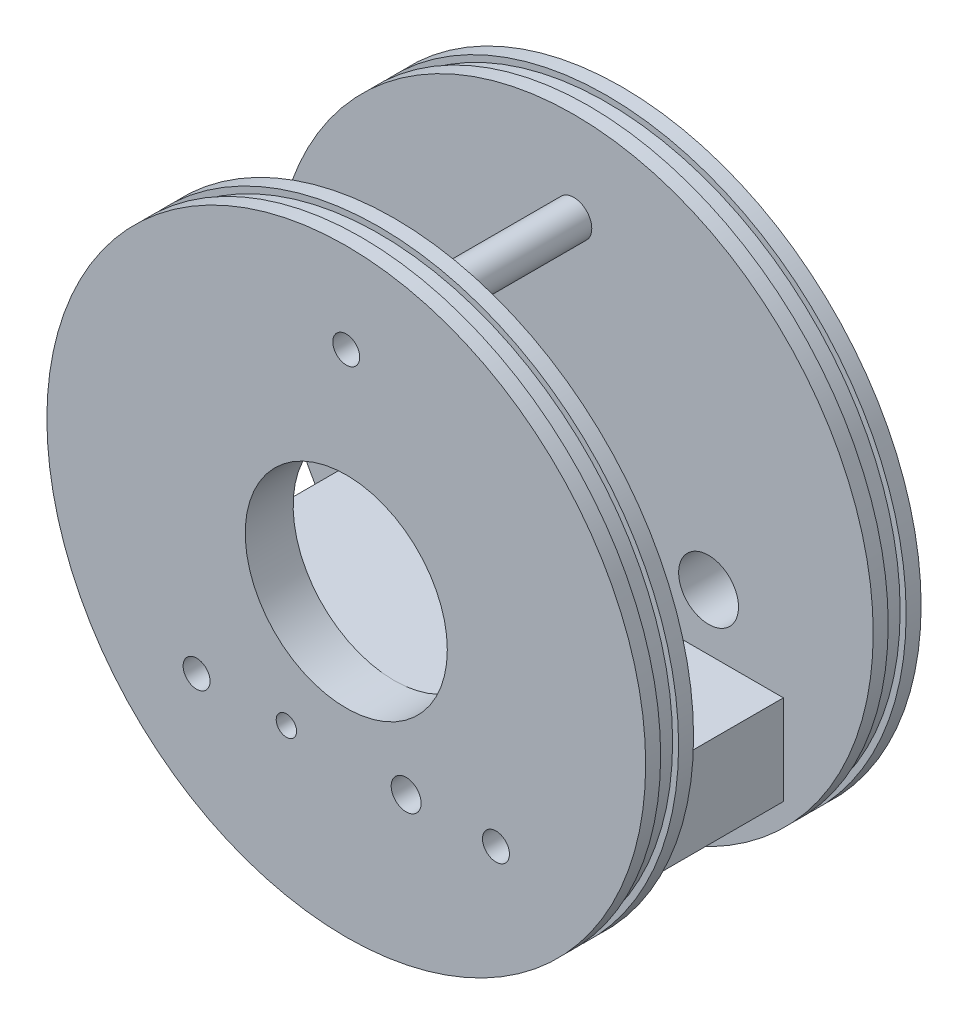
SolidWorks part; units mm, degrees
ref_plane "Front Plane" through (0, 0, 0) normal (0, 0, 1) x (1, 0, 0)
ref_plane "Top Plane" through (0, 0, 0) normal (0, 1, 0) x (1, 0, 0)
ref_plane "Right Plane" through (0, 0, 0) normal (1, 0, 0) x (0, 0, -1)
sketch "Sketch2" plane through (0, 0, 0) normal (0, 0, 1) x (1, 0, 0)
  circle A0 centre (0, 0) radius 98
  circle A1 centre (0, 0) radius 100
  dimension "D1" = 196
  dimension "D2" = 200
extrude "Boss-Extrude1" add sketch "Sketch2" along normal blind 8 and the other way blind 8 contours A1 A0 | A0 region at (-99.7172, 0, 0)
extrude "Cut-Extrude1" cut sketch "Sketch2<5>" against normal blind 3 and the other way blind 3
sketch "Sketch2<5>" plane through (0, 0, 0) normal (0, 0, 1) x (1, 0, 0) same geometry as "Sketch2"
sketch "Sketch3" plane through (0, 0, 8) normal (0, 0, 1) x (1, 0, 0)
  line L0 (0, 33.75) -> (0, -33.75) construction
  line L1 (41.5, 33.75) -> (-78.5, 33.75)
  line L2 (41.5, 33.75) -> (41.5, -33.75)
  line L3 (41.5, -33.75) -> (-78.5, -33.75) construction
  line L4 (-78.5, 33.75) -> (-78.5, -33.75) construction
  line L5 (31, 33.75) -> (31, -33.75) construction
  line L6 (41.5, 0) -> (-78.5, 0) construction
  line L7 (-78.5, 28.75) -> (-43.5, 28.75)
  line L8 (-43.5, 28.75) -> (-43.5, -33.75)
  line L9 (-78.5, 33.75) -> (-78.5, 28.75)
  line L10 (-43.5, -33.75) -> (41.5, -33.75)
  circle A0 centre (0, 0) radius 31
  circle A1 centre (0, 0) radius 33.75
  point P9 (0, 0)
  dimension "D3" = 62
  dimension "D7" = 67.5
  dimension "D1" = 10.5
  dimension "D2" = 120
  dimension "D4" = 67.5
  dimension "D5" = 5
  dimension "D6" = 35
sketch "Sketch4" plane through (0, 0, -8) normal (0, 0, 1) x (1, 0, 0)
  line L0 (0, 33.75) -> (0, -33.75) construction
  line L1 (41.5, 33.75) -> (-78.5, 33.75)
  line L2 (41.5, 33.75) -> (41.5, -33.75)
  line L3 (41.5, -33.75) -> (-78.5, -33.75) construction
  line L4 (-78.5, 33.75) -> (-78.5, -33.75) construction
  line L5 (31, 33.75) -> (31, -33.75) construction
  line L6 (41.5, 0) -> (-78.5, 0) construction
  line L7 (-78.5, 28.75) -> (-43.5, 28.75)
  line L8 (-43.5, 28.75) -> (-43.5, -33.75)
  line L9 (-78.5, 33.75) -> (-78.5, 28.75)
  line L10 (-43.5, -33.75) -> (41.5, -33.75)
  circle A0 centre (0, 0) radius 31
  point P9 (0, 0)
  point P16 (204.2739, 34.924)
  point P18 (372.8764, 103.8868)
  point P19 (0, 0)
  point P21 (0, 0)
  dimension "D3" = 62
  dimension "D1" = 10.5
  dimension "D2" = 120
  dimension "D4" = 67.5
  dimension "D5" = 5
  dimension "D6" = 35
ref_plane "Plane1" through (0, -33.75, 0) normal (0, 1, 0) x (1, 0, 0)
pattern_linear "LPattern1" count 2 spacing 76 along (0, 0, -1) of bodies 102 105
sketch "Sketch5" plane through (0, -33.75, 0) normal (0, 1, 0) x (1, 0, 0)
  line L0 (0, 8) -> (0, 43) construction
  line L1 (70, 8) -> (-70, 8)
  line L2 (70, 8) -> (70, 68)
  line L3 (70, 68) -> (-70, 68)
  line L4 (-70, 8) -> (-70, 68)
  circle A0 centre (0, 43) radius 3.2
  dimension "D4" = 6.4
  dimension "D1" = 60
  dimension "D2" = 140
  dimension "D3" = 35
extrude "Boss-Extrude2" add sketch "Sketch5" against normal blind 30 contours A0 | L3 L4 L1 L2 region at (0, -33.75, -43)
sketch "Sketch7" plane through (0, 0, 8) normal (0, 0, 1) x (1, 0, 0)
  line L0 (0, -33.75) -> (0, -48.75) construction
  line L1 (-50, -48.75) -> (50, -48.75) construction
  line L2 (0, -48.75) -> (20, -48.75) construction
  line L3 (0, -48.75) -> (-20, -48.75) construction
  circle A0 centre (-50, -48.75) radius 4.5
  circle A1 centre (50, -48.75) radius 4.5
  circle A3 centre (-20, -48.75) radius 3.4
  circle A4 centre (20, -48.75) radius 5
  point P7 (0, -48.75)
  dimension "D3" = 9
  dimension "D4" = 9
  dimension "D5" = 20
  dimension "D7" = 6.8
  dimension "D8" = 10
  dimension "D1" = 100
  dimension "D2" = 15
  dimension "D6" = 20
extrude "Cut-Extrude2" cut sketch "Sketch7" against normal blind 167
extrude "Cut-Extrude3" cut sketch "Sketch3" against normal blind 43 contours L1 A1 L10 A0 | A0 | A1 region at (23.1899, 23.1899, 8) region at (0, 0, 8)
sketch "Sketch10" plane through (0, 0, -8) normal (0, 0, -1) x (-1, 0, 0)
  line L0 (0, 0) -> (0, 70) construction
  circle A0 centre (0, 70) radius 4.5
  circle A1 centre (0, 70) radius 6
  dimension "D2" = 9
  dimension "D3" = 12
  dimension "D1" = 70
extrude "Boss-Extrude3" add sketch "Sketch10" along normal blind 60 contours A1
extrude "Cut-Extrude4" cut sketch "Sketch10<4>" against normal blind 60 and the other way blind 112 contours A0 region at (0, 70, -8)
sketch "Sketch10<4>" plane through (0, 0, -8) normal (0, 0, -1) x (-1, 0, 0) same geometry as "Sketch10"
sketch "Sketch11" plane through (0, 0, -84) normal (0, 0, -1) x (-1, 0, 0)
  line L0 (0, 0) -> (0, -15) construction
  line L1 (0, -15) -> (-45, -15) construction
  circle A0 centre (-45, -15) radius 10
  point P6 (-44.8091, -24.1819)
  dimension "D3" = 20
  dimension "D1" = 15
  dimension "D2" = 45
extrude "Cut-Extrude5" cut sketch "Sketch11" against normal blind 60 contours A0
